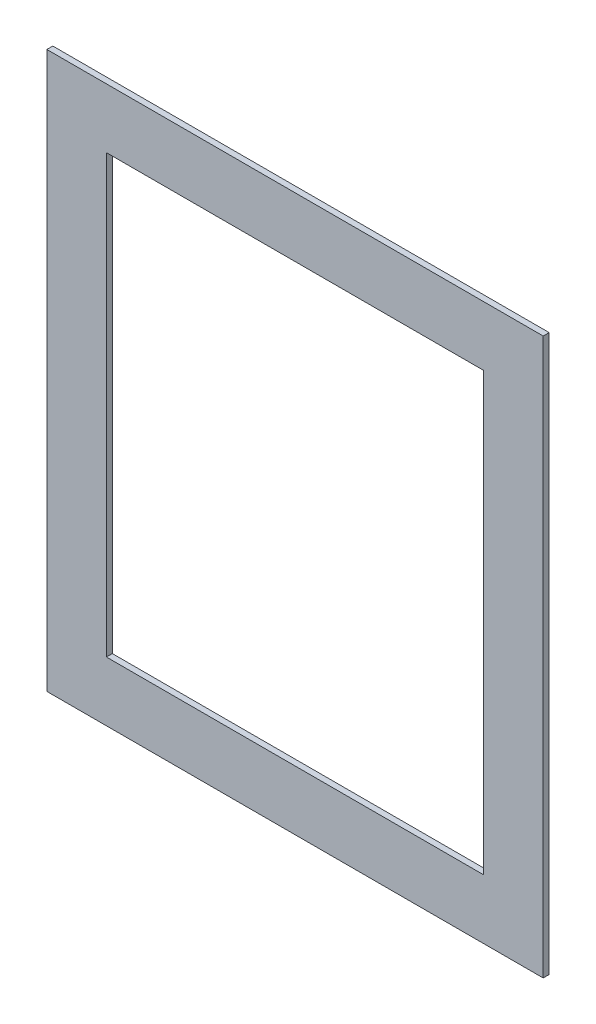
SolidWorks part; units mm, degrees
material "Клен"
ref_plane "Спереди" through (0, 0, 0) normal (0, 0, 1) x (1, 0, 0)
ref_plane "Сверху" through (0, 0, 0) normal (0, 1, 0) x (1, 0, 0)
ref_plane "Справа" through (0, 0, 0) normal (1, 0, 0) x (0, 0, -1)
sketch "Эскиз1" plane through (0, 0, 0) normal (0, 0, 1) x (1, 0, 0)
  line L0 (2.3279, 480.4642) -> (2.3279, 40.4642)
  line L1 (-57.6721, 540.4642) -> (442.3279, 540.4642)
  line L2 (-57.6721, 540.4642) -> (-57.6721, -19.5358)
  line L3 (-57.6721, -19.5358) -> (442.3279, -19.5358)
  line L4 (442.3279, 540.4642) -> (442.3279, -19.5358)
  line L5 (2.3279, 40.4642) -> (382.3279, 40.4642)
  line L6 (382.3279, 480.4642) -> (382.3279, 40.4642)
  line L7 (2.3279, 480.4642) -> (382.3279, 480.4642)
  dimension "D1" = 60
  dimension "D2" = 500
  dimension "D3" = 60
  dimension "D4" = 380
  dimension "D5" = 60
  dimension "D6" = 60
extrude "Бобышка-Вытянуть1" add sketch "Эскиз1" along normal blind 6
equation "\"sheet_thickness\"= 6"
equation "\"D1@Бобышка-Вытянуть1\"= \"sheet_thickness\""
equation "\"bottom_line\"= 60"
equation "\"width_space\"= 500"
equation "\"D6@Эскиз1\"=\"D5@Эскиз1\""
